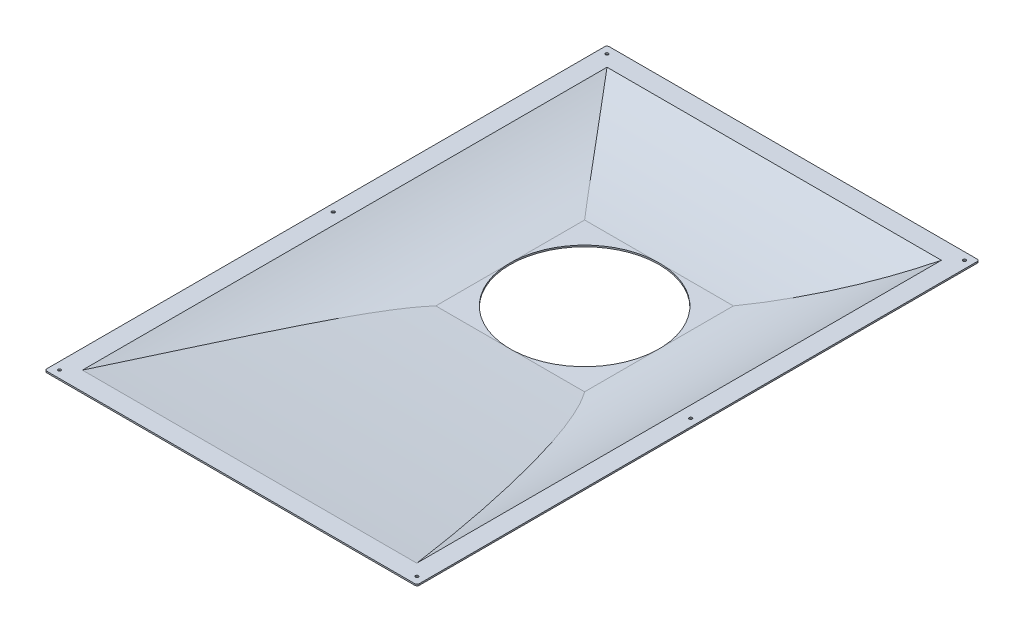
SolidWorks part; units mm, degrees
ref_plane "Ön Düzlem" through (0, 0, 0) normal (0, 0, 1) x (1, 0, 0)
ref_plane "Üst Düzlem" through (0, 0, 0) normal (0, 1, 0) x (1, 0, 0)
ref_plane "Sağ Düzlem" through (0, 0, 0) normal (1, 0, 0) x (0, 0, -1)
sketch "Sketch1" plane through (0, 0, 0) normal (0, 1, 0) x (1, 0, 0)
  line L1 (-250, -375) -> (0, -375)
  line L2 (-250, -375) -> (-250, 380)
  line L3 (-250, 380) -> (0, 380)
  line L4 (0, -375) -> (0, 380)
  line L5 (-250, -375) -> (0, 380) construction
  line L6 (-250, 380) -> (0, -375) construction
  point P0 (0, 0)
  dimension "D1" = 250
  dimension "D2" = 755
  dimension "D3" = 250
extrude "Boss-Extrude1" add sketch "Sketch1" along normal blind 40
sketch "Sketch2" plane through (0, 0, 0) normal (0, -1, 0) x (1, 0, 0)
  circle A0 centre (0, -100) radius 100
  dimension "D1" = 100
ref_plane "Plane1" through (0, 0, -100) normal (0, 0, 1) x (1, 0, 0)
sketch "Sketch6" plane through (0, 0, -100) normal (0, 0, 1) x (1, 0, 0)
  line L0 (-100, 0) -> (100, 0) construction
  line L1 (-250, 0) -> (0, 0) construction
  line L2 (-250, 40) -> (0, 40) construction
  line L3 (-225, 38) -> (-250, 38)
  line L4 (-250, 40) -> (-250, 0) construction
  line L5 (-250, 38) -> (-250, 40)
  line L6 (-100, 0) -> (0, 0)
  line L7 (0, 0) -> (0, -20.1592)
  line L8 (0, -20.1592) -> (-273.2342, -20.1592)
  line L9 (-273.2342, -20.1592) -> (-273.2342, 40)
  line L10 (-273.2342, 40) -> (-250, 40)
  arc A0 (-225, 38) -> (-100, 0) centre (-66.7005, 334.13) ccw
  dimension "D1" = 2
  dimension "D2" = 25
extrude "Cut-Extrude1" cut sketch "Sketch6" against normal through all both and the other way through all contours L9 L10 L5 L3 A0 L6 L7 L8
mirror "Mirror2" about plane through (0, 0, 0) normal (1, 0, 0) of "Cut-Extrude1", "Boss-Extrude1"
sketch "Sketch9" plane through (0, 0, 0) normal (1, 0, 0) x (0, 0, -1)
  line L0 (200, 0) -> (0, 0)
  line L1 (0, 0) -> (200, 0) construction
  line L2 (380, 38) -> (-375, 38) construction
  line L3 (355, 38) -> (394.867, 38)
  line L4 (394.867, 38) -> (394.867, -19.964)
  line L5 (394.867, -19.964) -> (-417.3641, -19.964)
  line L6 (-417.3641, -19.964) -> (-417.3641, 38)
  line L7 (380, 38) -> (-375, 38) construction
  line L8 (-350, 38) -> (-417.3641, 38)
  arc A0 (200, 0) -> (355, 38) centre (155.4367, 516.8898) ccw
  arc A1 (0, 0) -> (-350, 38) centre (408.6494, 5394.7177) cw
  dimension "D1" = 25
  dimension "D2" = 25
extrude "Cut-Extrude2" cut sketch "Sketch9" against normal through all both and the other way through all
shell "Shell1" thickness 2 removed face at (0, 40, -2.5)
extrude "Cut-Extrude6" cut sketch "Sketch2" against normal up to next
sketch "Sketch10" plane through (0, 40, 0) normal (0, 1, 0) x (1, 0, 0)
  line L0 (-224.4982, 2.3702) -> (-250, 2.5) construction
  line L1 (-224.4982, 354.5996) -> (-224.4982, -349.8591) construction
  line L2 (-250, 380) -> (-250, -375) construction
  line L3 (-250, -375) -> (-224.4982, -349.8591) construction
  line L4 (0, 380) -> (0, -375) construction
  line L5 (250, 380) -> (-250, 380) construction
  line L8 (-250, -375) -> (250, -375) construction
  line L9 (-224.4982, 354.5996) -> (-250, 380) construction
  circle A0 centre (-240, 2.4491) radius 2
  circle A1 centre (-240, -365.1415) radius 2
  circle A2 centre (240, 370.0397) radius 2
  circle A3 centre (240, 2.4491) radius 2
  circle A4 centre (240, -365.1415) radius 2
  circle A5 centre (-240, 370.0397) radius 2
  dimension "D1" = 10
  dimension "D2" = 10
  dimension "D6" = 10
extrude "Cut-Extrude7" cut sketch "Sketch10" against normal up to next
fillet "Fillet1" radius 3 4 edges at (-250, 39, 375) (250, 39, 375) (250, 39, -380) (-250, 39, -380)
